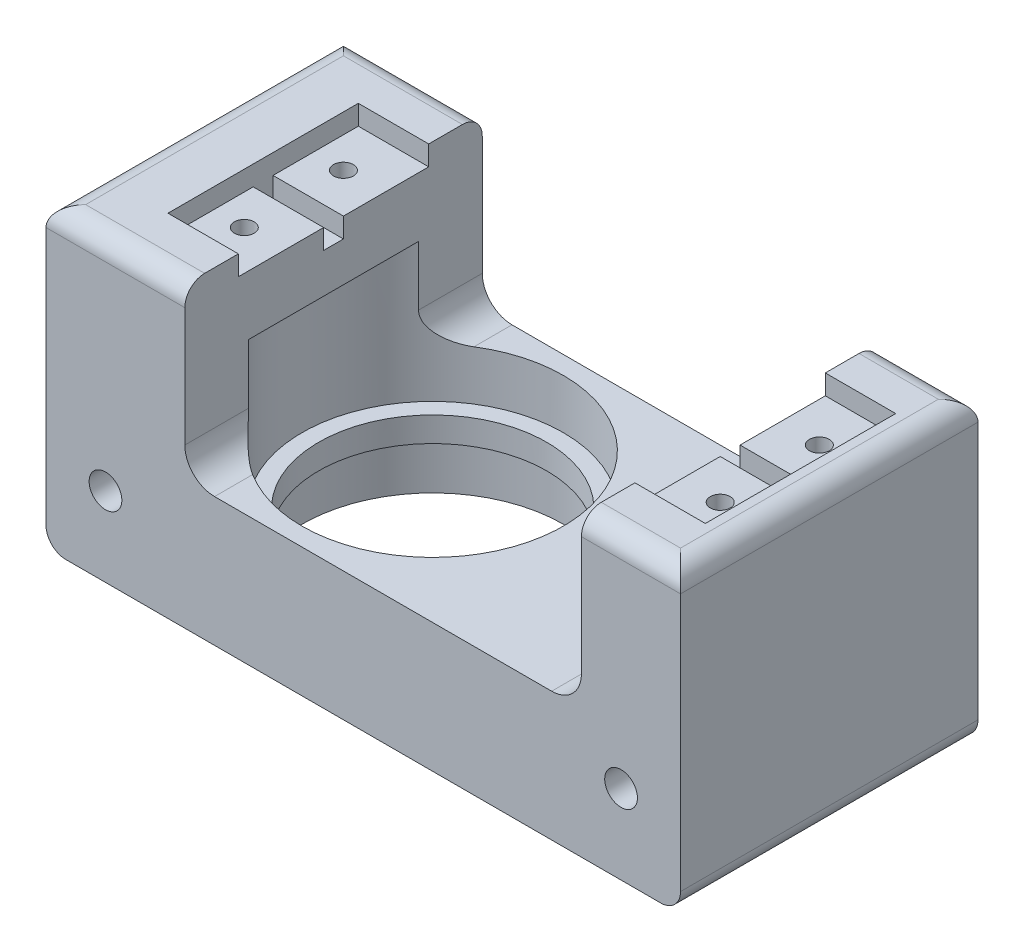
SolidWorks part; units mm, degrees
ref_plane "Спереди" through (0, 0, 0) normal (0, 0, 1) x (1, 0, 0)
ref_plane "Сверху" through (0, 0, 0) normal (0, 1, 0) x (1, 0, 0)
ref_plane "Справа" through (0, 0, 0) normal (1, 0, 0) x (0, 0, -1)
sketch "Эскиз1" plane through (0, 0, 0) normal (0, 1, 0) x (1, 0, 0)
  line L0 (0, 15) -> (0, -15) construction
  line L1 (-24, 15) -> (40, 15)
  line L2 (-24, 15) -> (-24, -15)
  line L3 (-24, -15) -> (40, -15)
  line L4 (40, 15) -> (40, -15)
  line L6 (-24, 0) -> (40, 0) construction
  point P6 (0, 0)
  dimension "D1" = 30
  dimension "D2" = 24
  dimension "D3" = 40
extrude "тело для подшипников" add sketch "Эскиз1" along normal blind 13
sketch "Эскиз2" plane through (0, 13, 0) normal (0, 1, 0) x (1, 0, 0)
  circle A0 centre (0, 0) radius 13.175
  dimension "D1" = 26.35
extrude "подшипник верхний" cut sketch "Эскиз2" against normal blind 5
sketch "Эскиз3" plane through (0, 0, 0) normal (0, -1, 0) x (1, 0, 0)
  circle A0 centre (0, 0) radius 13.175
  dimension "D1" = 26.35
extrude "подшипник нижний" cut sketch "Эскиз3" against normal blind 5.5
sketch "Эскиз4" plane through (0, 8, 0) normal (0, 1, 0) x (1, 0, 0)
  circle A0 centre (0, 0) radius 11.5
  dimension "D1" = 23
extrude "отверстие под ось" cut sketch "Эскиз4" against normal through all
sketch "Эскиз8" plane through (0, 13, 0) normal (0, 1, 0) x (1, 0, 0)
  line L0 (-24, 0) -> (40, 0) construction
  line L1 (-24, 15) -> (40, 15)
  line L2 (-24, 15) -> (-24, -15)
  line L3 (-24, -15) -> (40, -15)
  line L4 (40, 15) -> (40, -15)
  line L5 (-24, 15) -> (-24, -15) construction
  line L6 (0, 15) -> (0, -15) construction
  circle A0 centre (0, 0) radius 13.175
  circle A1 centre (0, 0) radius 13.175 construction
  dimension "D2" = 40
extrude "основание под сервой" add sketch "Эскиз8" along normal blind 3
sketch "Эскиз9" plane through (0, 16, 0) normal (0, 1, 0) x (1, 0, 0)
  line L0 (40, 15) -> (-24, 15) construction
  line L1 (-20, 15) -> (-10, 15)
  line L2 (-20, 15) -> (-20, -15)
  line L3 (-20, -15) -> (-10, -15)
  line L4 (-10, 15) -> (-10, 8.5779)
  line L5 (-24, -15) -> (40, -15) construction
  line L6 (0, 15) -> (0, -15) construction
  line L7 (40, 15) -> (30, 15)
  line L8 (40, 15) -> (40, -15)
  line L9 (40, -15) -> (30, -15)
  line L10 (30, 15) -> (30, -15)
  line L11 (-10, -8.5779) -> (-10, -15)
  line L12 (-24, 15) -> (-24, -15) construction
  arc A0 (-10, 8.5779) -> (-10, -8.5779) centre (0, 0) ccw
  circle A1 centre (0, 0) radius 13.175 construction
  dimension "D1" = 20
  dimension "D2" = 40
  dimension "D3" = 10
  dimension "D4" = 10
extrude "выступы к серве" add sketch "Эскиз9" along normal blind 12
sketch "Эскиз10" plane through (0, 28, 0) normal (0, 1, 0) x (1, 0, 0)
  line L0 (-20, 0) -> (40, 0) construction
  line L1 (-20, 15) -> (-20, -15) construction
  line L2 (40, -15) -> (40, 15) construction
  line L3 (-14, 5) -> (-14, -5) construction
  line L5 (34, 5) -> (34, -5) construction
  circle A0 centre (-14, 5) radius 1
  circle A1 centre (-14, -5) radius 1
  circle A2 centre (34, -5) radius 1
  circle A3 centre (34, 5) radius 1
  point P14 (34, 0)
  point P15 (-14, 0)
  dimension "D1" = 2
  dimension "D2" = 10
  dimension "D3" = 14
  dimension "D4" = 34
extrude "крепление сервы" cut sketch "Эскиз10" against normal blind 12
sketch "Эскиз11" plane through (0, 0, 15) normal (0, 0, 1) x (1, 0, 0)
  line L0 (-24, 8) -> (40, 8) construction
  line L1 (-24, 16) -> (-24, 0) construction
  line L2 (40, 28) -> (40, 0) construction
  line L4 (0, 16) -> (0, 0) construction
  line L5 (8, 0) -> (8, 16) construction
  line L6 (-10, 16) -> (30, 16) construction
  line L8 (-24, 0) -> (40, 0) construction
  circle A0 centre (-18, 8) radius 1.65
  circle A3 centre (34, 8) radius 1.65
  dimension "D1" = 3.3
  dimension "D2" = 52
extrude "отверстия под болты" cut sketch "Эскиз11" against normal through all
sketch "Эскиз12" plane through (0, 28, 0) normal (0, 1, 0) x (1, 0, 0)
  line L0 (-10, -15) -> (-10, -8.5779) construction
  line L1 (-10, 8.5779) -> (-10, 15) construction
  line L2 (-20, 15) -> (-10, 15)
  line L3 (-20, 15) -> (-20, 9.6)
  line L4 (-20, 9.6) -> (-10, 9.6)
  line L5 (-20, -15) -> (-10, -15)
  line L6 (-10, 15) -> (-10, 9.6)
  line L7 (-20, -15) -> (-20, -9.6)
  line L8 (-20, -9.6) -> (-10, -9.6)
  line L9 (-10, -15) -> (-10, -9.6)
  line L10 (30, 15) -> (30, -15) construction
  line L11 (40, -15) -> (30, -15)
  line L12 (40, -15) -> (40, -9.6)
  line L13 (40, -9.6) -> (30, -9.6)
  line L14 (30, -15) -> (30, -9.6)
  line L15 (40, 15) -> (30, 15) construction
  line L16 (40, 15) -> (30, 15)
  line L17 (40, 15) -> (40, 9.6)
  line L18 (40, 9.6) -> (30, 9.6)
  line L19 (30, 15) -> (30, 9.6)
  line L20 (40, -15) -> (40, 15) construction
  dimension "D1" = 5.4
extrude "бортики к серве" add sketch "Эскиз12" along normal blind 2
sketch "Эскиз14" plane through (0, 16, 0) normal (0, 1, 0) x (1, 0, 0)
  line L0 (-10, 15) -> (-10, 8.5779)
  line L1 (-10, 15) -> (30, 15)
  line L2 (30, 15) -> (30, -15)
  line L3 (30, -15) -> (-10, -15)
  line L4 (-10, -15) -> (-10, -8.5779)
  arc A0 (-10, -8.5779) -> (-10, 8.5779) centre (0, 0) ccw
  arc A1 (-10, -8.5779) -> (-10, 8.5779) centre (0, 0) ccw construction
extrude "углубление впресовать подшипник" cut sketch "Эскиз14" against normal blind 3
sketch "Эскиз15" plane through (0, 28, 0) normal (0, 1, 0) x (1, 0, 0)
  line L1 (-20, 9.6) -> (-10, 9.6)
  line L2 (-20, 9.6) -> (-20, -9.6)
  line L3 (-20, -9.6) -> (-10, -9.6)
  line L4 (-10, 9.6) -> (-10, -9.6)
  circle A0 centre (-14, 5) radius 1
  circle A1 centre (-14, -5) radius 1
  circle A2 centre (-14, 5) radius 1 construction
  circle A3 centre (-14, -5) radius 1 construction
extrude "наплыв для саморезов" add sketch "Эскиз15" against normal blind 9
chamfer "Фаска5" distance 3 angle 45 1 edges at (-10, 19, 0)
sketch "Эскиз17" plane through (0, 28, 0) normal (0, 1, 0) x (1, 0, 0)
  line L0 (-10, -9.6) -> (-20, -9.6) construction
  line L1 (-20, 9.6) -> (-17.1, 9.6)
  line L2 (-20, 9.6) -> (-20, -9.6)
  line L3 (-20, -9.6) -> (-17.1, -9.6)
  line L4 (-17.1, 9.6) -> (-17.1, -9.6)
  line L5 (40, -9.6) -> (30, -9.6) construction
  line L6 (40, 9.6) -> (37.1, 9.6)
  line L7 (40, 9.6) -> (40, -9.6)
  line L8 (40, -9.6) -> (37.1, -9.6)
  line L9 (37.1, 9.6) -> (37.1, -9.6)
  line L10 (-20, 9.6) -> (-10, 9.6) construction
  line L11 (-20, 15) -> (-20, -15) construction
  line L12 (-20, 9.6) -> (-20, -9.6) construction
  dimension "D1" = 2.9
  dimension "D2" = 2.9
extrude "бортики к серве спереди" add sketch "Эскиз17" along normal up to surface (2 mm away) up to face at (-15, 30, -12.3)
sketch "Эскиз16" plane through (0, 28, 0) normal (0, 1, 0) x (1, 0, 0)
  line L0 (-17.1, 0) -> (37.1, 0) construction
  line L3 (-10, -9.6) -> (-10, 9.6) construction
  line L4 (-10, 1) -> (-17.1, 1)
  line L5 (-10, 1) -> (-10, -1)
  line L6 (-10, -1) -> (-17.1, -1)
  line L7 (-17.1, 1) -> (-17.1, -1)
  line L8 (30, 9.6) -> (30, -9.6) construction
  line L9 (30, -1) -> (37.1, -1)
  line L10 (30, -1) -> (30, 1)
  line L11 (30, 1) -> (37.1, 1)
  line L12 (37.1, -1) -> (37.1, 1)
  line L13 (-17.1, -9.6) -> (-17.1, 9.6) construction
  line L14 (-17.1, -9.6) -> (-17.1, 9.6) construction
  line L15 (37.1, 9.6) -> (37.1, -9.6) construction
  point P12 (-10, 0)
  point P19 (30, 0)
  dimension "D1" = 2
extrude "пазы под ребра жесткости сервы" cut sketch "Эскиз16" against normal blind 2
sketch "Эскиз18" plane through (0, 16, 0) normal (0, 1, 0) x (1, 0, 0)
  line L0 (-20, -15) -> (-10, -15) construction
  line L1 (-24, 15) -> (-20, 15)
  line L2 (-24, 15) -> (-24, -15)
  line L3 (-24, -15) -> (-20, -15)
  line L4 (-20, 15) -> (-20, -15)
  line L5 (-20, 15) -> (-20, -15) construction
extrude "площадка под светодиод" add sketch "Эскиз18" along normal up to surface (14 mm away) up to face at (-14.275, 30, 0)
fillet "Скругление4" radius 3 3 edges at (30, 13, 0) (-10, 13, -11.789) (-10, 13, 11.789)
fillet "Скругление5" radius 2 8 edges at (-24, 0, 0) (40, 0, 0) (35, 30, 15) (40, 30, 0) (35, 30, -15) (-17, 30, 15) (-24, 30, 0) (-17, 30, -15)
